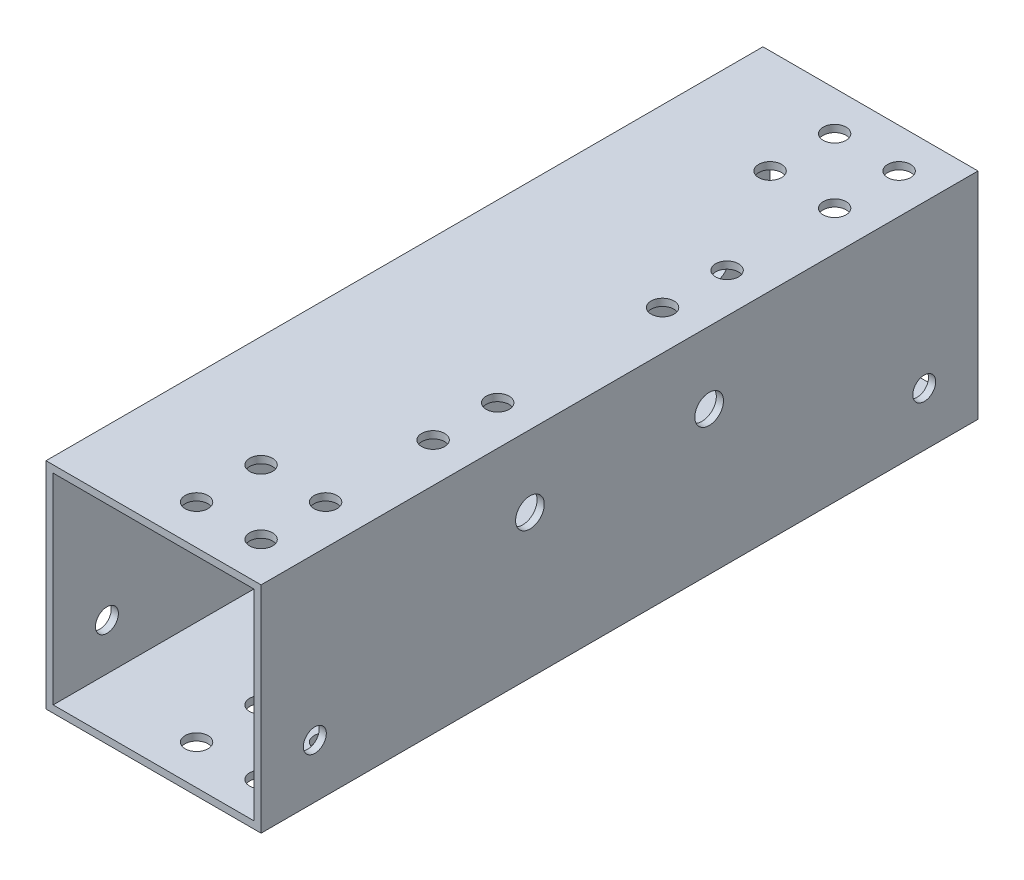
SolidWorks part; units mm, degrees
material "6061-T6 (SS)"
ref_plane "前视基准面" through (0, 0, 0) normal (0, 0, 1) x (1, 0, 0)
ref_plane "上视基准面" through (0, 0, 0) normal (0, 1, 0) x (1, 0, 0)
ref_plane "右视基准面" through (0, 0, 0) normal (1, 0, 0) x (0, 0, -1)
sketch "草图1" plane through (0, 0, 0) normal (0, 0, 1) x (1, 0, 0)
  line L1 (-15, 15) -> (15, 15)
  line L2 (-15, 15) -> (-15, -15)
  line L3 (-15, -15) -> (15, -15)
  line L4 (15, 15) -> (15, -15)
  line L5 (-15, 15) -> (15, -15) construction
  line L6 (-15, -15) -> (15, 15) construction
  line L7 (-14, 14) -> (14, 14)
  line L8 (-14, 14) -> (-14, -14)
  line L9 (-14, -14) -> (14, -14)
  line L10 (14, 14) -> (14, -14)
  line L11 (-14, 14) -> (14, -14) construction
  line L12 (-14, -14) -> (14, 14) construction
  point P0 (0, 0)
  point P6 (0, 0)
  dimension "D1" = 30
  dimension "D2" = 30
  dimension "D3" = 28
  dimension "D4" = 28
extrude "凸台-拉伸1" add sketch "草图1" along normal blind 100
sketch "草图3" plane through (0, 15, 0) normal (0, 1, 0) x (1, 0, 0)
  line L1 (15, -100) -> (-5, -100) construction
  line L2 (15, -100) -> (15, -80) construction
  line L3 (15, -80) -> (-5, -80) construction
  line L4 (-5, -100) -> (-5, -80) construction
  line L5 (15, -100) -> (-5, -80) construction
  line L6 (15, -80) -> (-5, -100) construction
  line L7 (0.5, -85.5) -> (9.5, -85.5) construction
  line L8 (0.5, -85.5) -> (0.5, -94.5) construction
  line L9 (0.5, -94.5) -> (9.5, -94.5) construction
  line L10 (9.5, -85.5) -> (9.5, -94.5) construction
  line L11 (0.5, -85.5) -> (9.5, -94.5) construction
  line L12 (0.5, -94.5) -> (9.5, -85.5) construction
  line L13 (-15, 0) -> (15, 0) construction
  line L14 (-15, 0) -> (-15, -100) construction
  line L15 (-15, -100) -> (15, -100) construction
  line L16 (15, 0) -> (15, -100) construction
  line L17 (0, -100) -> (0, 0) construction
  line L18 (-15, -50) -> (15, -50) construction
  circle A0 centre (0.5, -94.5) radius 1.6
  circle A1 centre (9.5, -94.5) radius 1.6
  circle A2 centre (9.5, -85.5) radius 1.6
  circle A3 centre (0.5, -85.5) radius 1.6
  circle A4 centre (9.5, -14.5) radius 1.6
  circle A5 centre (9.5, -5.5) radius 1.6
  circle A6 centre (0.5, -5.5) radius 1.6
  circle A7 centre (0.5, -14.5) radius 1.6
  circle A8 centre (9.5, -70.5) radius 1.6
  circle A9 centre (9.5, -61.5) radius 1.6
  circle A10 centre (9.5, -38.5) radius 1.6
  circle A11 centre (9.5, -29.5) radius 1.6
  point P4 (5, -90)
  point P6 (5, -90)
  point P258 (0, -50)
  dimension "D4" = 2
  dimension "D1" = 20
  dimension "D2" = 20
  dimension "D3" = 9
  dimension "D5" = 2
  dimension "D6" = 2
extrude "切除-拉伸1" cut sketch "草图3" against normal through all
sketch "草图5" plane through (15, 0, 0) normal (1, 0, 0) x (0, 0, -1)
  line L0 (-100, -15) -> (0, -15) construction
  line L1 (-100, 15) -> (-85, 15) construction
  line L2 (-100, 15) -> (-100, -15) construction
  line L3 (-100, -15) -> (-85, -15) construction
  line L4 (-85, 15) -> (-85, -15) construction
  line L5 (-92.5, -15) -> (-92.5, 15) construction
  line L6 (-100, 0) -> (-85, 0) construction
  line L8 (-100, -15) -> (-85, -15) construction
  line L9 (-100, -15) -> (-100, 0) construction
  line L10 (-100, 0) -> (-85, 0) construction
  line L11 (-85, -15) -> (-85, 0) construction
  line L12 (-92.5, 0) -> (-92.5, -15) construction
  line L13 (-100, -7.5) -> (-85, -7.5) construction
  circle A0 centre (-92.5, -7.5) radius 1.6
  circle A1 centre (-7.5, -7.5) radius 1.6
  point P160 (-92.5, -7.5)
  point P196 (-92.5, 0)
  dimension "D3" = 2
  dimension "D1" = 15
  dimension "D2" = 15
extrude "切除-拉伸3" cut sketch "草图5" against normal through all
sketch "草图6" plane through (15, 0, 0) normal (1, 0, 0) x (0, 0, -1)
  line L1 (-100, 15) -> (0, 15) construction
  line L2 (-100, 15) -> (-100, -15) construction
  line L3 (-100, -15) -> (0, -15) construction
  line L4 (0, 15) -> (0, -15) construction
  line L5 (-50, -15) -> (-50, 15) construction
  line L6 (-100, 0) -> (0, 0) construction
  line L7 (-62.5, 5) -> (-37.5, 5) construction
  line L8 (-62.5, 5) -> (-62.5, -5) construction
  line L9 (-62.5, -5) -> (-37.5, -5) construction
  line L10 (-37.5, 5) -> (-37.5, -5) construction
  line L11 (-62.5, 5) -> (-37.5, -5) construction
  line L12 (-62.5, -5) -> (-37.5, 5) construction
  circle A0 centre (-62.5, 5) radius 2
  circle A1 centre (-37.5, 5) radius 2
  point P4 (-50, 0)
  point P364 (-50, 0)
  dimension "D1" = 25
  dimension "D2" = 10
extrude "切除-拉伸4" cut sketch "草图6" against normal through all
